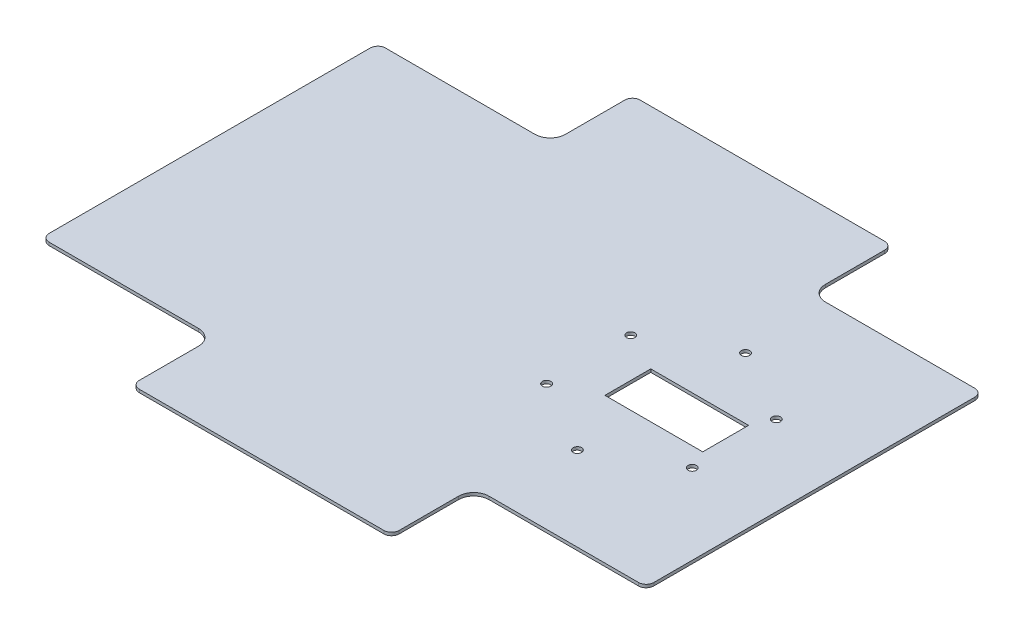
SolidWorks part; units mm, degrees
material "7075-T6, Пластина (SS)"
ref_plane "Спереди" through (0, 0, 0) normal (0, 0, 1) x (1, 0, 0)
ref_plane "Сверху" through (0, 0, 0) normal (0, 1, 0) x (1, 0, 0)
ref_plane "Справа" through (0, 0, 0) normal (1, 0, 0) x (0, 0, -1)
sketch "Эскиз1" plane through (0, 0, 0) normal (0, 1, 0) x (1, 0, 0)
  line L1 (-80, -163.8055) -> (80, -163.8055)
  line L2 (-197.7687, -105) -> (-197.7687, 105)
  line L3 (-80, 163.8055) -> (80, 163.8055)
  line L4 (197.7687, -105) -> (197.7687, 105)
  line L5 (-236.4266, 144.4996) -> (-147.9018, 144.4996) construction
  line L6 (-147.9018, 144.4996) -> (286.4952, 144.4996) construction
  line L18 (-284.5497, 0) -> (284.3305, 0) construction
  line L19 (-160.9018, 110) -> (-134.9018, 110)
  line L20 (-160.9018, 110) -> (-160.9018, 0)
  line L21 (-160.9018, 0) -> (-134.9018, 0)
  line L22 (-134.9018, 110) -> (-134.9018, 0)
  line L23 (-147.9018, -182.6295) -> (-147.9018, 219.9923) construction
  line L24 (-160.9018, 0) -> (-134.9018, 0)
  line L25 (-160.9018, 0) -> (-160.9018, -110)
  line L26 (-160.9018, -110) -> (-134.9018, -110)
  line L27 (-134.9018, 0) -> (-134.9018, -110)
  line L28 (-97.9018, -119.4996) -> (-197.9018, -119.4996)
  line L29 (-97.9018, 169.4996) -> (-197.9018, 169.4996)
  line L30 (-97.9018, 169.4996) -> (-97.9018, 119.4996)
  line L31 (-97.9018, 119.4996) -> (-197.9018, 119.4996)
  line L32 (-197.9018, 169.4996) -> (-197.9018, 119.4996)
  line L33 (-97.9018, 169.4996) -> (-197.9018, 119.4996) construction
  line L34 (-97.9018, 119.4996) -> (-197.9018, 169.4996) construction
  line L35 (-197.9018, -169.4996) -> (-197.9018, -119.4996)
  line L36 (-97.9018, -169.4996) -> (-197.9018, -169.4996)
  line L37 (-97.9018, -169.4996) -> (-97.9018, -119.4996)
  line L39 (-85, 120) -> (-85, 158.8055)
  line L40 (0, 262.7398) -> (0, -186.5795) construction
  line L41 (-192.7687, 110) -> (-95, 110)
  line L43 (-192.7687, -110) -> (-95, -110)
  line L44 (-85, -120) -> (-85, -158.8055)
  line L45 (85, 120) -> (85, 158.8055)
  line L46 (192.7687, 110) -> (95, 110)
  line L47 (192.7687, -110) -> (95, -110)
  line L48 (85, -120) -> (85, -158.8055)
  line L49 (97.9018, -169.4996) -> (97.9018, -119.4996)
  line L50 (97.9018, -169.4996) -> (197.9018, -169.4996)
  line L51 (197.9018, -169.4996) -> (197.9018, -119.4996)
  line L52 (97.9018, -119.4996) -> (197.9018, -119.4996)
  line L53 (160.9018, 0) -> (160.9018, -110)
  line L54 (160.9018, -110) -> (134.9018, -110)
  line L55 (134.9018, 0) -> (134.9018, -110)
  line L56 (160.9018, 0) -> (134.9018, 0)
  line L57 (160.9018, 110) -> (160.9018, 0)
  line L58 (160.9018, 0) -> (134.9018, 0)
  line L59 (134.9018, 110) -> (134.9018, 0)
  line L60 (160.9018, 110) -> (134.9018, 110)
  line L61 (97.9018, 119.4996) -> (197.9018, 119.4996)
  line L62 (197.9018, 169.4996) -> (197.9018, 119.4996)
  line L63 (97.9018, 169.4996) -> (197.9018, 169.4996)
  line L64 (97.9018, 169.4996) -> (97.9018, 119.4996)
  arc A0 (85, -120) -> (95, -110) centre (95, -120) cw
  arc A1 (85, 120) -> (95, 110) centre (95, 120) ccw
  arc A2 (-95, -110) -> (-85, -120) centre (-95, -120) cw
  arc A3 (-85, 120) -> (-95, 110) centre (-95, 120) cw
  arc A4 (192.7687, -110) -> (197.7687, -105) centre (192.7687, -105) ccw
  arc A5 (85, -158.8055) -> (80, -163.8055) centre (80, -158.8055) cw
  arc A6 (-85, -158.8055) -> (-80, -163.8055) centre (-80, -158.8055) ccw
  arc A7 (-192.7687, -110) -> (-197.7687, -105) centre (-192.7687, -105) cw
  arc A8 (-192.7687, 110) -> (-197.7687, 105) centre (-192.7687, 105) ccw
  arc A9 (197.7687, 105) -> (192.7687, 110) centre (192.7687, 105) ccw
  arc A10 (85, 158.8055) -> (80, 163.8055) centre (80, 158.8055) ccw
  arc A11 (-85, 158.8055) -> (-80, 163.8055) centre (-80, 158.8055) cw
  point P0 (0, 0)
  point P3 (85, -110)
  point P17 (-147.9018, 110)
  point P18 (-147.9018, 110)
  point P20 (-147.9018, 0)
  point P22 (-150, 134)
  point P37 (-147.9018, 144.4996)
  point P46 (85, 110)
  point P52 (-85, -110)
  point P55 (-85, 110)
  point P56 (-147.9018, 0)
  point P77 (197.7687, -110)
  point P80 (85, -163.8055)
  point P83 (-85, -163.8055)
  point P86 (-197.7687, -110)
  point P89 (-197.7687, 110)
  point P92 (197.7687, 110)
  point P95 (85, 163.8055)
  point P98 (-85, 163.8055)
  dimension "D2" = 50
  dimension "D6" = 10
  dimension "D4" = 5
  dimension "D3" = 26
  dimension "D5" = 338.9991
  dimension "D7" = 395.5373
  dimension "D8" = 110
  dimension "D9" = 170
  dimension "D10" = 100
  dimension "D13" = 9.4996
  dimension "D14" = 12.9018
sketch "Эскиз2" plane through (0, 0, 0) normal (0, 1, 0) x (1, 0, 0)
  line L0 (-162.9105, 114) -> (-136.9105, 114)
  line L1 (-162.9105, 114) -> (-162.9105, 0)
  line L2 (-162.9105, 0) -> (-136.9105, 0)
  line L3 (-136.9105, 114) -> (-136.9105, 0)
  line L4 (-149.9105, -192.6295) -> (-149.9105, 209.9923) construction
  line L5 (-162.9105, 0) -> (-136.9105, 0)
  line L6 (-162.9105, 0) -> (-162.9105, -114)
  line L7 (-162.9105, -114) -> (-136.9105, -114)
  line L8 (-136.9105, 0) -> (-136.9105, -114)
  line L9 (-99.9105, -123.5568) -> (-199.9105, -123.5568)
  line L10 (-99.9105, 163.4996) -> (-199.9105, 163.4996)
  line L11 (-99.9105, 163.4996) -> (-99.9105, 123.4996)
  line L12 (-99.9105, 123.4996) -> (-199.9105, 123.4996)
  line L13 (-199.9105, 163.4996) -> (-199.9105, 123.4996)
  line L14 (-199.9105, -163.5568) -> (-199.9105, -123.5568)
  line L15 (-99.9105, -163.5568) -> (-199.9105, -163.5568)
  line L16 (-99.9105, -163.5568) -> (-99.9105, -123.5568)
  line L17 (-284.5497, 0) -> (284.3305, 0) construction
  point P11 (-149.9105, 0)
  point P12 (-149.9105, 0)
sketch "Эскиз3" plane through (0, 0, 0) normal (0, 1, 0) x (1, 0, 0)
  line L0 (-89.8176, -177.9027) -> (70.2405, -177.9027)
  line L1 (-209.7886, -106.9112) -> (-209.7886, 106.8353)
  line L2 (-80.029, 172.0973) -> (50.2405, 172.0973)
  line L3 (170.2114, -106.9112) -> (170.2114, 103.9123)
  line L4 (-87.1938, 124.0033) -> (-87.1938, 164.9326)
  line L5 (-202.6239, 114) -> (-97.1971, 114)
  line L6 (-202.6239, -114.076) -> (-106.9857, -114.076)
  line L7 (-96.9823, -124.0793) -> (-96.9823, -170.738)
  line L8 (57.4052, 121.0803) -> (57.4052, 164.9326)
  line L9 (163.0467, 111.077) -> (67.4085, 111.077)
  line L10 (163.0467, -114.076) -> (87.4085, -114.076)
  line L11 (77.4052, -124.0793) -> (77.4052, -170.738)
  line L13 (-162.9105, 114) -> (-136.9105, 114) construction
  arc A0 (77.4052, -124.0793) -> (87.4085, -114.076) centre (87.4085, -124.0793) cw
  arc A1 (57.4052, 121.0803) -> (67.4085, 111.077) centre (67.4085, 121.0803) ccw
  arc A2 (-106.9857, -114.076) -> (-96.9823, -124.0793) centre (-106.9857, -124.0793) cw
  arc A3 (-87.1938, 124.0033) -> (-97.1971, 114) centre (-97.1971, 124.0033) cw
  arc A4 (-80.029, 172.0973) -> (-87.1938, 164.9326) centre (-80.029, 164.9326) ccw
  arc A5 (50.2405, 172.0973) -> (57.4052, 164.9326) centre (50.2405, 164.9326) cw
  arc A6 (170.2114, 103.9123) -> (163.0467, 111.077) centre (163.0467, 103.9123) ccw
  arc A7 (170.2114, -106.9112) -> (163.0467, -114.076) centre (163.0467, -106.9112) cw
  arc A8 (70.2405, -177.9027) -> (77.4052, -170.738) centre (70.2405, -170.738) ccw
  arc A9 (-89.8176, -177.9027) -> (-96.9823, -170.738) centre (-89.8176, -170.738) cw
  arc A10 (-209.7886, -106.9112) -> (-202.6239, -114.076) centre (-202.6239, -106.9112) ccw
  arc A11 (-209.7886, 106.8353) -> (-202.6239, 114) centre (-202.6239, 106.8353) cw
  point P36 (115.2276, 111.077)
  point P39 (-149.9105, 114)
  point P42 (-149.9105, 114)
  dimension "D3" = 10.0033
  dimension "D4" = 7.1647
  dimension "D1" = 380
  dimension "D2" = 350
  dimension "D5" = 112.8062
  dimension "D6" = 63.8267
  dimension "D7" = 61.0203
extrude "Бобышка-Вытянуть1" add sketch "Эскиз1" along normal blind 2 separate body contours A11 L39 A3 L41 L22 L27 L43 A2 L44 A6 L1 A5 L48 A0 L47 L55 L59 L46 A1 L45 A10 L3 | L4 A9 L46 L57 L53 L47 A4 | L46 L59 L56 L57 | L53 L56 L55 L47 | L27 L21 L25 L26 | L41 A8 L2 A7 L43 L25 L20 | L22 L19 L20 L21 region at (0, 0, 0) region at (-147.9018, 0, 55) region at (147.9018, 0, 55) region at (-179.3123, 0, 0) region at (-147.9018, 0, -55) region at (179.3123, 0, 0) region at (147.9018, 0, -55)
sketch "Эскиз4" plane through (0, 2, 0) normal (0, 1, 0) x (1, 0, 0)
  line L0 (197.7687, 0) -> (-197.7687, 0) construction
  line L1 (197.7687, -105) -> (197.7687, 105) construction
  line L2 (-197.7687, -105) -> (-197.7687, 105) construction
  line L3 (197.7687, 0) -> (107.7687, 0) construction
  line L4 (75.7687, 0) -> (97.7687, 0) construction
  line L5 (97.7687, 0) -> (97.7687, 55) construction
  line L11 (139.7687, -15) -> (75.7687, -15)
  line L12 (139.7687, -15) -> (139.7687, 15)
  line L13 (139.7687, 15) -> (75.7687, 15)
  line L14 (75.7687, -15) -> (75.7687, 15)
  line L15 (139.7687, -15) -> (75.7687, 15) construction
  line L16 (139.7687, 15) -> (75.7687, -15) construction
  circle A1 centre (97.7687, 55) radius 2.75
  circle A2 centre (145.4001, 27.5) radius 2.75
  circle A3 centre (145.4001, -27.5) radius 2.75
  circle A4 centre (97.7687, -55) radius 2.75
  circle A5 centre (50.1373, -27.5) radius 2.75
  circle A6 centre (50.1373, 27.5) radius 2.75
  point P14 (97.7687, 0)
  point P16 (0, 0)
  point P17 (0, 0)
  point P29 (97.7687, 0)
  dimension "D1" = 6
  dimension "D2" = 5.5
  dimension "D3" = 64
  dimension "D4" = 30
  dimension "D5" = 55
  dimension "D6" = 22
extrude "Вырез-Вытянуть1" cut sketch "Эскиз4" against normal through all
